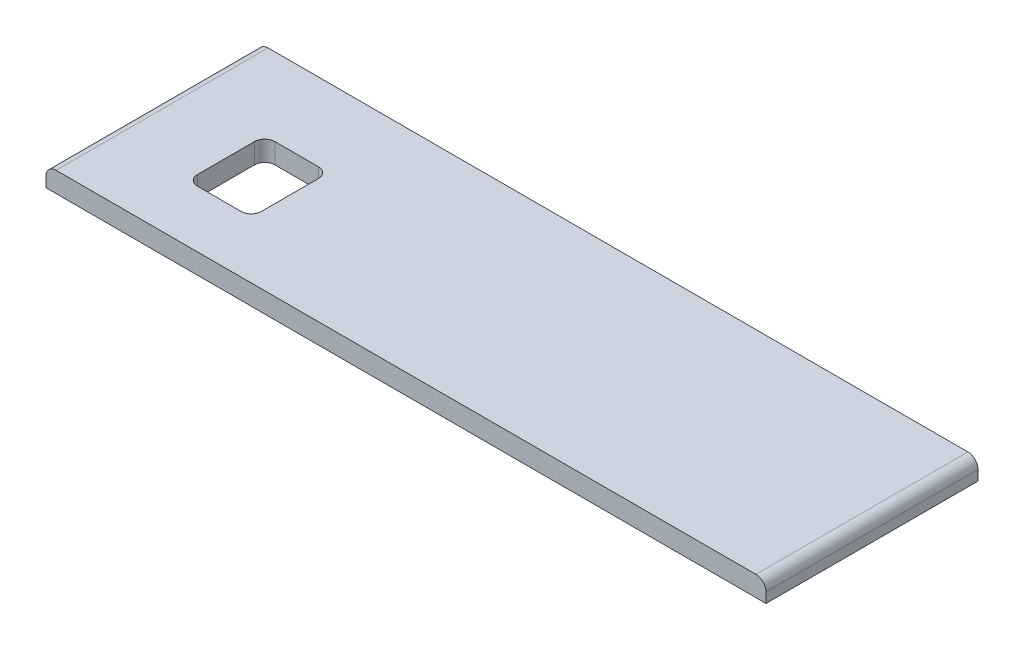
SolidWorks part; units mm, degrees
ref_plane "Спереди" through (0, 0, 0) normal (0, 0, 1) x (1, 0, 0)
ref_plane "Сверху" through (0, 0, 0) normal (0, 1, 0) x (1, 0, 0)
ref_plane "Справа" through (0, 0, 0) normal (1, 0, 0) x (0, 0, -1)
other "Configuration Table"
sketch "Эскиз1" plane through (0, 0, 0) normal (0, 1, 0) x (1, 0, 0)
  line L1 (0, -31.5) -> (107, -31.5)
  line L2 (0, -31.5) -> (0, 0)
  line L3 (0, 0) -> (107, 0)
  line L4 (107, -31.5) -> (107, 0)
  line L5 (12.55, -23.05) -> (22.05, -23.05)
  line L6 (12.55, -23.05) -> (12.55, -11.55)
  line L7 (12.55, -11.55) -> (22.05, -11.55)
  line L8 (22.05, -23.05) -> (22.05, -11.55)
extrude "Бобышка-Вытянуть1" add sketch "Эскиз1" along normal blind 3
fillet "tool_D3_R1p5_power_corners" radius 1.5 4 edges at (12.55, 1.5, 11.55) (22.05, 1.5, 11.55) (22.05, 1.5, 23.05) (12.55, 1.5, 23.05) tangent propagation no
fillet "tool_D3_R1p5_rear_outer_corners" radius 1.5 2 edges at (0, 3, 15.75) (107, 3, 15.75)
